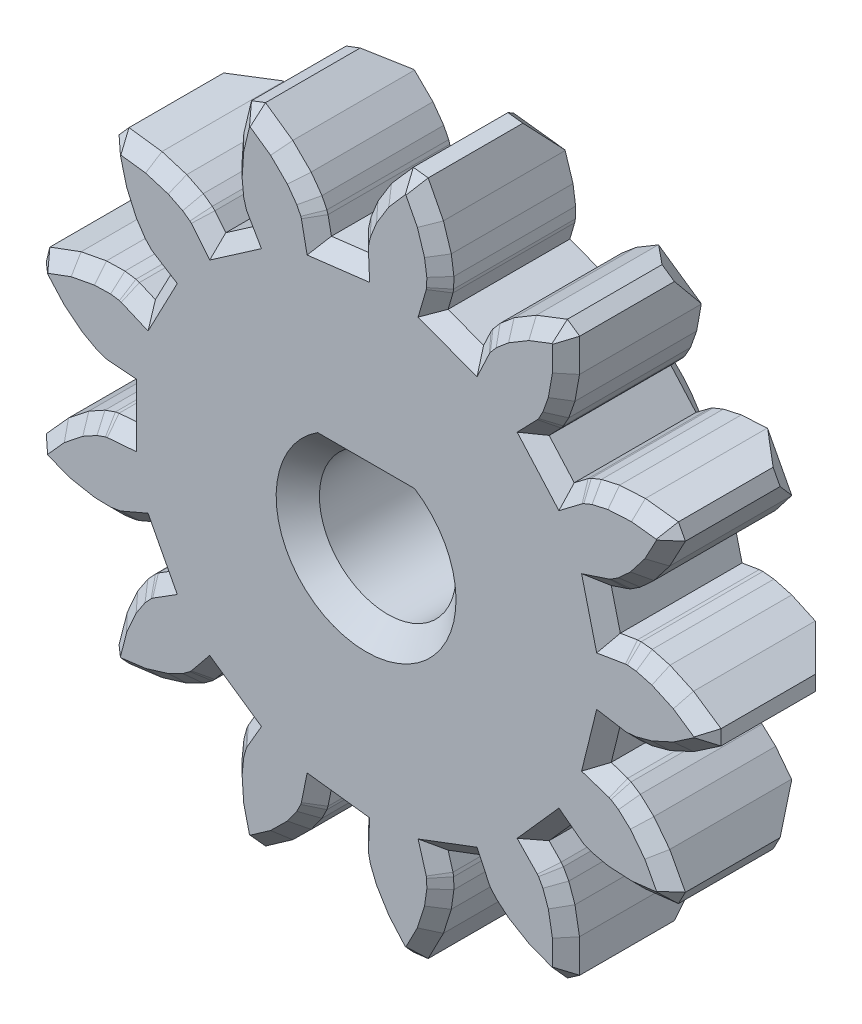
SolidWorks part; units mm, degrees
material "Custom Plastic"
ref_plane "Front Plane" through (0, 0, 0) normal (0, 0, 1) x (1, 0, 0)
ref_plane "Top Plane" through (0, 0, 0) normal (0, 1, 0) x (1, 0, 0)
ref_plane "Right Plane" through (0, 0, 0) normal (1, 0, 0) x (0, 0, -1)
sketch "Model" plane through (0, 0, 0) normal (0, 0, 1) x (1, 0, 0)
  line L0 (-12.322, -2.752) -> (-11.499, -1.837)
  line L1 (-11.499, -1.837) -> (-10.75, -1.243)
  line L2 (-10.75, -1.243) -> (-10.152, -0.913)
  line L3 (-10.152, -0.913) -> (-9.766, -0.777)
  line L4 (-9.766, -0.777) -> (-9.632, -0.751)
  line L5 (-9.632, -0.751) -> (-8.992, -0.701)
  line L6 (-8.992, -0.701) -> (-8.992, 0.701)
  line L7 (-8.992, 0.701) -> (-9.632, 0.751)
  line L8 (-9.632, 0.751) -> (-9.766, 0.777)
  line L9 (-9.766, 0.777) -> (-10.152, 0.913)
  line L10 (-10.152, 0.913) -> (-10.75, 1.243)
  line L11 (-10.75, 1.243) -> (-11.499, 1.837)
  line L12 (-11.499, 1.837) -> (-12.322, 2.752)
  line L13 (-12.322, 2.752) -> (-12.189, 3.29)
  line L14 (-12.189, 3.29) -> (-11.036, 3.717)
  line L15 (-11.036, 3.717) -> (-10.096, 3.895)
  line L16 (-10.096, 3.895) -> (-9.414, 3.91)
  line L17 (-9.414, 3.91) -> (-9.008, 3.851)
  line L18 (-9.008, 3.851) -> (-8.878, 3.811)
  line L19 (-8.878, 3.811) -> (-8.288, 3.558)
  line L20 (-8.288, 3.558) -> (-7.637, 4.8)
  line L21 (-7.637, 4.8) -> (-8.18, 5.141)
  line L22 (-8.18, 5.141) -> (-8.286, 5.226)
  line L23 (-8.286, 5.226) -> (-8.565, 5.527)
  line L24 (-8.565, 5.527) -> (-8.941, 6.096)
  line L25 (-8.941, 6.096) -> (-9.328, 6.971)
  line L26 (-9.328, 6.971) -> (-9.631, 8.163)
  line L27 (-9.631, 8.163) -> (-9.264, 8.577)
  line L28 (-9.264, 8.577) -> (-8.045, 8.42)
  line L29 (-8.045, 8.42) -> (-7.129, 8.141)
  line L30 (-7.129, 8.141) -> (-6.519, 7.837)
  line L31 (-6.519, 7.837) -> (-6.187, 7.596)
  line L32 (-6.187, 7.596) -> (-6.09, 7.501)
  line L33 (-6.09, 7.501) -> (-5.685, 7.002)
  line L34 (-5.685, 7.002) -> (-4.532, 7.799)
  line L35 (-4.532, 7.799) -> (-4.854, 8.354)
  line L36 (-4.854, 8.354) -> (-4.908, 8.478)
  line L37 (-4.908, 8.478) -> (-5.016, 8.874)
  line L38 (-5.016, 8.874) -> (-5.084, 9.553)
  line L39 (-5.084, 9.553) -> (-5.02, 10.508)
  line L40 (-5.02, 10.508) -> (-4.735, 11.704)
  line L41 (-4.735, 11.704) -> (-4.217, 11.9)
  line L42 (-4.217, 11.9) -> (-3.21, 11.194)
  line L43 (-3.21, 11.194) -> (-2.529, 10.522)
  line L44 (-2.529, 10.522) -> (-2.13, 9.968)
  line L45 (-2.13, 9.968) -> (-1.948, 9.601)
  line L46 (-1.948, 9.601) -> (-1.907, 9.471)
  line L47 (-1.907, 9.471) -> (-1.78, 8.842)
  line L48 (-1.78, 8.842) -> (-0.388, 9.011)
  line L49 (-0.388, 9.011) -> (-0.416, 9.652)
  line L50 (-0.416, 9.652) -> (-0.406, 9.788)
  line L51 (-0.406, 9.788) -> (-0.317, 10.189)
  line L52 (-0.317, 10.189) -> (-0.062, 10.821)
  line L53 (-0.062, 10.821) -> (0.438, 11.637)
  line L54 (0.438, 11.637) -> (1.246, 12.563)
  line L55 (1.246, 12.563) -> (1.796, 12.497)
  line L56 (1.796, 12.497) -> (2.36, 11.404)
  line L57 (2.36, 11.404) -> (2.65, 10.492)
  line L58 (2.65, 10.492) -> (2.746, 9.817)
  line L59 (2.746, 9.817) -> (2.737, 9.407)
  line L60 (2.737, 9.407) -> (2.713, 9.273)
  line L61 (2.713, 9.273) -> (2.533, 8.657)
  line L62 (2.533, 8.657) -> (3.845, 8.16)
  line L63 (3.845, 8.16) -> (4.118, 8.74)
  line L64 (4.118, 8.74) -> (4.189, 8.856)
  line L65 (4.189, 8.856) -> (4.454, 9.169)
  line L66 (4.454, 9.169) -> (4.974, 9.611)
  line L67 (4.974, 9.611) -> (5.796, 10.101)
  line L68 (5.796, 10.101) -> (6.942, 10.545)
  line L69 (6.942, 10.545) -> (7.398, 10.23)
  line L70 (7.398, 10.23) -> (7.389, 9.001)
  line L71 (7.389, 9.001) -> (7.222, 8.059)
  line L72 (7.222, 8.059) -> (6.994, 7.416)
  line L73 (6.994, 7.416) -> (6.795, 7.057)
  line L74 (6.795, 7.057) -> (6.712, 6.949)
  line L75 (6.712, 6.949) -> (6.266, 6.487)
  line L76 (6.266, 6.487) -> (7.196, 5.438)
  line L77 (7.196, 5.438) -> (7.708, 5.825)
  line L78 (7.708, 5.825) -> (7.825, 5.895)
  line L79 (7.825, 5.895) -> (8.205, 6.049)
  line L80 (8.205, 6.049) -> (8.871, 6.198)
  line L81 (8.871, 6.198) -> (9.826, 6.25)
  line L82 (9.826, 6.25) -> (11.047, 6.111)
  line L83 (11.047, 6.111) -> (11.305, 5.62)
  line L84 (11.305, 5.62) -> (10.726, 4.536)
  line L85 (10.726, 4.536) -> (10.14, 3.779)
  line L86 (10.14, 3.779) -> (9.639, 3.316)
  line L87 (9.639, 3.316) -> (9.296, 3.091)
  line L88 (9.296, 3.091) -> (9.173, 3.034)
  line L89 (9.173, 3.034) -> (8.563, 2.832)
  line L90 (8.563, 2.832) -> (8.899, 1.471)
  line L91 (8.899, 1.471) -> (9.532, 1.576)
  line L92 (9.532, 1.576) -> (9.668, 1.583)
  line L93 (9.668, 1.583) -> (10.076, 1.543)
  line L94 (10.076, 1.543) -> (10.735, 1.366)
  line L95 (10.735, 1.366) -> (11.605, 0.968)
  line L96 (11.605, 0.968) -> (12.622, 0.277)
  line L97 (12.622, 0.277) -> (12.622, -0.277)
  line L98 (12.622, -0.277) -> (11.605, -0.968)
  line L99 (11.605, -0.968) -> (10.735, -1.366)
  line L100 (10.735, -1.366) -> (10.076, -1.543)
  line L101 (10.076, -1.543) -> (9.668, -1.583)
  line L102 (9.668, -1.583) -> (9.532, -1.576)
  line L103 (9.532, -1.576) -> (8.899, -1.471)
  line L104 (8.899, -1.471) -> (8.563, -2.832)
  line L105 (8.563, -2.832) -> (9.173, -3.034)
  line L106 (9.173, -3.034) -> (9.296, -3.091)
  line L107 (9.296, -3.091) -> (9.639, -3.316)
  line L108 (9.639, -3.316) -> (10.14, -3.779)
  line L109 (10.14, -3.779) -> (10.726, -4.536)
  line L110 (10.726, -4.536) -> (11.305, -5.62)
  line L111 (11.305, -5.62) -> (11.047, -6.111)
  line L112 (11.047, -6.111) -> (9.826, -6.25)
  line L113 (9.826, -6.25) -> (8.871, -6.198)
  line L114 (8.871, -6.198) -> (8.205, -6.049)
  line L115 (8.205, -6.049) -> (7.825, -5.895)
  line L116 (7.825, -5.895) -> (7.708, -5.825)
  line L117 (7.708, -5.825) -> (7.196, -5.438)
  line L118 (7.196, -5.438) -> (6.266, -6.487)
  line L119 (6.266, -6.487) -> (6.712, -6.949)
  line L120 (6.712, -6.949) -> (6.795, -7.057)
  line L121 (6.795, -7.057) -> (6.994, -7.416)
  line L122 (6.994, -7.416) -> (7.222, -8.059)
  line L123 (7.222, -8.059) -> (7.389, -9.001)
  line L124 (7.389, -9.001) -> (7.398, -10.23)
  line L125 (7.398, -10.23) -> (6.942, -10.545)
  line L126 (6.942, -10.545) -> (5.796, -10.101)
  line L127 (5.796, -10.101) -> (4.974, -9.611)
  line L128 (4.974, -9.611) -> (4.454, -9.169)
  line L129 (4.454, -9.169) -> (4.189, -8.856)
  line L130 (4.189, -8.856) -> (4.118, -8.74)
  line L131 (4.118, -8.74) -> (3.845, -8.16)
  line L132 (3.845, -8.16) -> (2.533, -8.657)
  line L133 (2.533, -8.657) -> (2.713, -9.273)
  line L134 (2.713, -9.273) -> (2.737, -9.407)
  line L135 (2.737, -9.407) -> (2.746, -9.817)
  line L136 (2.746, -9.817) -> (2.65, -10.492)
  line L137 (2.65, -10.492) -> (2.36, -11.404)
  line L138 (2.36, -11.404) -> (1.796, -12.497)
  line L139 (1.796, -12.497) -> (1.246, -12.563)
  line L140 (1.246, -12.563) -> (0.438, -11.637)
  line L141 (0.438, -11.637) -> (-0.062, -10.821)
  line L142 (-0.062, -10.821) -> (-0.317, -10.189)
  line L143 (-0.317, -10.189) -> (-0.406, -9.788)
  line L144 (-0.406, -9.788) -> (-0.416, -9.652)
  line L145 (-0.416, -9.652) -> (-0.388, -9.011)
  line L146 (-0.388, -9.011) -> (-1.78, -8.842)
  line L147 (-1.78, -8.842) -> (-1.907, -9.471)
  line L148 (-1.907, -9.471) -> (-1.948, -9.601)
  line L149 (-1.948, -9.601) -> (-2.13, -9.968)
  line L150 (-2.13, -9.968) -> (-2.529, -10.522)
  line L151 (-2.529, -10.522) -> (-3.21, -11.194)
  line L152 (-3.21, -11.194) -> (-4.217, -11.9)
  line L153 (-4.217, -11.9) -> (-4.735, -11.704)
  line L154 (-4.735, -11.704) -> (-5.02, -10.508)
  line L155 (-5.02, -10.508) -> (-5.084, -9.553)
  line L156 (-5.084, -9.553) -> (-5.016, -8.874)
  line L157 (-5.016, -8.874) -> (-4.908, -8.478)
  line L158 (-4.908, -8.478) -> (-4.854, -8.354)
  line L159 (-4.854, -8.354) -> (-4.532, -7.799)
  line L160 (-4.532, -7.799) -> (-5.685, -7.002)
  line L161 (-5.685, -7.002) -> (-6.09, -7.501)
  line L162 (-6.09, -7.501) -> (-6.187, -7.596)
  line L163 (-6.187, -7.596) -> (-6.519, -7.837)
  line L164 (-6.519, -7.837) -> (-7.129, -8.141)
  line L165 (-7.129, -8.141) -> (-8.045, -8.42)
  line L166 (-8.045, -8.42) -> (-9.264, -8.577)
  line L167 (-9.264, -8.577) -> (-9.631, -8.163)
  line L168 (-9.631, -8.163) -> (-9.328, -6.971)
  line L169 (-9.328, -6.971) -> (-8.941, -6.096)
  line L170 (-8.941, -6.096) -> (-8.565, -5.527)
  line L171 (-8.565, -5.527) -> (-8.286, -5.226)
  line L172 (-8.286, -5.226) -> (-8.18, -5.141)
  line L173 (-8.18, -5.141) -> (-7.637, -4.8)
  line L174 (-7.637, -4.8) -> (-8.288, -3.558)
  line L175 (-8.288, -3.558) -> (-8.878, -3.811)
  line L176 (-8.878, -3.811) -> (-9.008, -3.851)
  line L177 (-9.008, -3.851) -> (-9.414, -3.91)
  line L178 (-9.414, -3.91) -> (-10.096, -3.895)
  line L179 (-10.096, -3.895) -> (-11.036, -3.717)
  line L180 (-11.036, -3.717) -> (-12.189, -3.29)
  line L181 (-12.189, -3.29) -> (-12.322, -2.752)
  line L182 (0, 0) -> (12.622, 0) construction
  line L183 (8.899, 1.471) -> (8.899, -1.471) construction
  line L184 (9.532, 1.576) -> (9.532, -1.576) construction
  line L185 (9.668, 1.583) -> (9.668, -1.583) construction
  line L186 (10.076, 1.543) -> (10.076, -1.543) construction
  line L187 (10.735, 1.366) -> (10.735, -1.366) construction
  line L188 (11.605, 0.968) -> (11.605, -0.968) construction
  circle A0 centre (0, 0) radius 1.5 construction
  dimension "D1" = 3
  dimension "D2" = 12.622
  dimension "D3" = 0.554
  dimension "D4" = 2.942
  dimension "D5" = 3.152
  dimension "D6" = 3.166
  dimension "D7" = 3.086
  dimension "D8" = 2.732
  dimension "D9" = 1.936
  dimension "D10" = 8.899
  dimension "D11" = 9.532
  dimension "D12" = 9.668
  dimension "D13" = 10.076
  dimension "D14" = 10.735
  dimension "D15" = 11.605
extrude "Boss-Extrude1" add sketch "Model" along normal blind 5
sketch "Sketch1" plane through (0, 0, 0) normal (0, 0, -1) x (-1, 0, 0)
  circle A0 centre (0, 0) radius 8
  dimension "D1" = 16
extrude "Boss-Extrude2" add sketch "Sketch1" along normal blind 3
sketch "Sketch2" plane through (0, 0, 5) normal (0, 0, 1) x (1, 0, 0)
  line L0 (-1.5413, 2) -> (1.5413, 2)
  arc A0 (-1.5413, 2) -> (1.5413, 2) centre (0, 0) ccw
  dimension "D1" = 5.05
  dimension "D2" = 2
extrude "Cut-Extrude1" cut sketch "Sketch2" against normal offset from surface (7.1 mm away) 0.9 up to face at (-8, 0, -3)
chamfer "Chamfer5" distance 1 distance2 1 13 edges at (11.176, 5.8655, 0) (12.622, 0, 0) (11.176, -5.8655, 0) (7.17, -10.3875, 0) (1.521, -12.53, 0) (-4.476, -11.802, 0) (-9.4475, -8.37, 0) (-12.2555, -3.021, 0) (-12.2555, 3.021, 0) (-9.4475, 8.37, 0) (-4.476, 11.802, 0) (1.521, 12.53, 0) (7.17, 10.3875, 0)
chamfer "Chamfer6" distance 0.5 angle 45 182 edges at (-11.9105, -2.2945, 5) (-11.1245, -1.54, 5) (-10.451, -1.078, 5) (-9.959, -0.845, 5) (-9.699, -0.764, 5) (-9.312, -0.726, 5) (-8.992, 0, 5) (-9.312, 0.726, 5) (-9.699, 0.764, 5) (-9.959, 0.845, 5) (-10.451, 1.078, 5) (-11.1245, 1.54, 5) (-11.9105, 2.2945, 5) (-11.6125, 3.5035, 5) (-10.566, 3.806, 5) (-9.755, 3.9025, 5) (-9.211, 3.8805, 5) (-8.943, 3.831, 5) (-8.583, 3.6845, 5) (-7.9625, 4.179, 5) (-7.9085, 4.9705, 5) (-8.233, 5.1835, 5) (-8.4255, 5.3765, 5) (-8.753, 5.8115, 5) (-9.1345, 6.5335, 5) (-9.4795, 7.567, 5) (-8.6545, 8.4985, 5) (-7.587, 8.2805, 5) (-6.824, 7.989, 5) (-6.353, 7.7165, 5) (-6.1385, 7.5485, 5) (-5.8875, 7.2515, 5) (-5.1085, 7.4005, 5) (-4.693, 8.0765, 5) (-4.881, 8.416, 5) (-4.962, 8.676, 5) (-5.05, 9.2135, 5) (-5.052, 10.0305, 5) (-4.8775, 11.106, 5) (-3.7135, 11.547, 5) (-2.8695, 10.858, 5) (-2.3295, 10.245, 5) (-2.039, 9.7845, 5) (-1.9275, 9.536, 5) (-1.8435, 9.1565, 5) (-1.084, 8.9265, 5) (-0.402, 9.3315, 5) (-0.411, 9.72, 5) (-0.3615, 9.9885, 5) (-0.1895, 10.505, 5) (0.188, 11.229, 5) (0.842, 12.1, 5) (2.078, 11.9505, 5) (2.505, 10.948, 5) (2.698, 10.1545, 5) (2.7415, 9.612, 5) (2.725, 9.34, 5) (2.623, 8.965, 5) (3.189, 8.4085, 5) (3.9815, 8.45, 5) (4.1535, 8.798, 5) (4.3215, 9.0125, 5) (4.714, 9.39, 5) (5.385, 9.856, 5) (6.369, 10.323, 5) (7.3935, 9.6155, 5) (7.3055, 8.53, 5) (7.108, 7.7375, 5) (6.8945, 7.2365, 5) (6.7535, 7.003, 5) (6.489, 6.718, 5) (6.731, 5.9625, 5) (7.452, 5.6315, 5) (7.7665, 5.86, 5) (8.015, 5.972, 5) (8.538, 6.1235, 5) (9.3485, 6.224, 5) (10.4365, 6.1805, 5) (11.0155, 5.078, 5) (10.433, 4.1575, 5) (9.8895, 3.5475, 5) (9.4675, 3.2035, 5) (9.2345, 3.0625, 5) (8.868, 2.933, 5) (8.731, 2.1515, 5) (9.2155, 1.5235, 5) (9.6, 1.5795, 5) (9.872, 1.563, 5) (10.4055, 1.4545, 5) (11.17, 1.167, 5) (12.1135, 0.6225, 5) (12.1135, -0.6225, 5) (11.17, -1.167, 5) (10.4055, -1.4545, 5) (9.872, -1.563, 5) (9.6, -1.5795, 5) (9.2155, -1.5235, 5) (8.731, -2.1515, 5) (8.868, -2.933, 5) (9.2345, -3.0625, 5) (9.4675, -3.2035, 5) (9.8895, -3.5475, 5) (10.433, -4.1575, 5) (11.0155, -5.078, 5) (10.4365, -6.1805, 5) (9.3485, -6.224, 5) (8.538, -6.1235, 5) (8.015, -5.972, 5) (7.7665, -5.86, 5) (7.452, -5.6315, 5) (6.731, -5.9625, 5) (6.489, -6.718, 5) (6.7535, -7.003, 5) (6.8945, -7.2365, 5) (7.108, -7.7375, 5) (7.3055, -8.53, 5) (7.3935, -9.6155, 5) (6.369, -10.323, 5) (5.385, -9.856, 5) (4.714, -9.39, 5) (4.3215, -9.0125, 5) (4.1535, -8.798, 5) (3.9815, -8.45, 5) (3.189, -8.4085, 5) (2.623, -8.965, 5) (2.725, -9.34, 5) (2.7415, -9.612, 5) (2.698, -10.1545, 5) (2.505, -10.948, 5) (2.078, -11.9505, 5) (0.842, -12.1, 5) (0.188, -11.229, 5) (-0.1895, -10.505, 5) (-0.3615, -9.9885, 5) (-0.411, -9.72, 5) (-0.402, -9.3315, 5) (-1.084, -8.9265, 5) (-1.8435, -9.1565, 5) (-1.9275, -9.536, 5) (-2.039, -9.7845, 5) (-2.3295, -10.245, 5) (-2.8695, -10.858, 5) (-3.7135, -11.547, 5) (-4.8775, -11.106, 5) (-5.052, -10.0305, 5) (-5.05, -9.2135, 5) (-4.962, -8.676, 5) (-4.881, -8.416, 5) (-4.693, -8.0765, 5) (-5.1085, -7.4005, 5) (-5.8875, -7.2515, 5) (-6.1385, -7.5485, 5) (-6.353, -7.7165, 5) (-6.824, -7.989, 5) (-7.587, -8.2805, 5) (-8.6545, -8.4985, 5) (-9.4795, -7.567, 5) (-9.1345, -6.5335, 5) (-8.753, -5.8115, 5) (-8.4255, -5.3765, 5) (-8.233, -5.1835, 5) (-7.9085, -4.9705, 5) (-7.9625, -4.179, 5) (-8.583, -3.6845, 5) (-8.943, -3.831, 5) (-9.211, -3.8805, 5) (-9.755, -3.9025, 5) (-10.566, -3.806, 5) (-11.6125, -3.5035, 5) (-12.2555, 3.021, 5) (-9.4475, 8.37, 5) (-4.476, 11.802, 5) (1.521, 12.53, 5) (7.17, 10.3875, 5) (11.176, 5.8655, 5) (12.622, 0, 5) (11.176, -5.8655, 5) (7.17, -10.3875, 5) (1.521, -12.53, 5) (-4.476, -11.802, 5) (-9.4475, -8.37, 5) (-12.2555, -3.021, 5)
sketch "Sketch3" plane through (0, 0, -3) normal (0, 0, -1) x (-1, 0, 0)
  circle A0 centre (0, 0) radius 2.525
  arc A1 (-1.5413, 2) -> (1.5413, 2) centre (0, 0) ccw construction
extrude "Cut-Extrude2" cut sketch "Sketch3" against normal up to surface (0.9 mm away) up to face at (0, -0.2625, -2.1)
chamfer "Chamfer7" [suppressed] distance 0.3 angle 45
chamfer "Chamfer8" distance 3 angle 45 1 edges at (-8, 0, -3)
chamfer "Chamfer9" distance 0.5 angle 60 1 edges at (-2.525, 0, -3) first distance on face at (-5, 0, -3)
chamfer "Chamfer10" distance 0.8 angle 45 2 edges at (0, 2, 5) (0, -2.525, 5)
